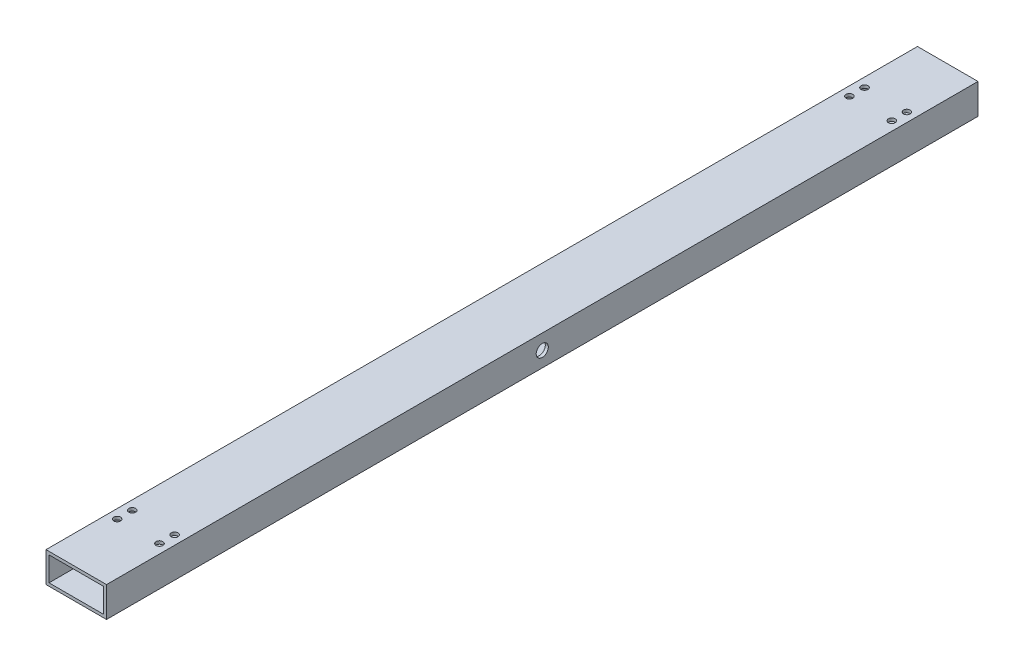
SolidWorks part; units mm, degrees
ref_plane "Front Plane" through (0, 0, 0) normal (0, 0, 1) x (1, 0, 0)
ref_plane "Top Plane" through (0, 0, 0) normal (0, 1, 0) x (1, 0, 0)
ref_plane "Right Plane" through (0, 0, 0) normal (1, 0, 0) x (0, 0, -1)
sketch "Sketch1" plane through (0, 0, 0) normal (0, 0, 1) x (1, 0, 0)
  line L0 (31.75, 0) -> (28.575, 0) construction
  line L1 (-31.75, 0) -> (31.75, 0) construction
  line L2 (0, 15.875) -> (0, -15.875)
  point P7 (0, 0)
  dimension "Width" = 63.5
  dimension "Wall Thickness" = 3.175
  dimension "Height" = 31.75
sketch "Sketch2" plane through (0, 0, 0) normal (1, 0, 0) x (0, 0, -1)
  line L0 (457.2, 0) -> (-457.2, 0)
  point P4 (0, 0)
  dimension "Length" = 914.4
sketch "Sketch3" plane through (0, 0, 0) normal (0, 0, 1) x (1, 0, 0)
  line L0 (0, 12.7) -> (0, 15.875) construction
  line L1 (-31.75, 15.875) -> (31.75, 15.875)
  line L2 (-31.75, 15.875) -> (-31.75, -15.875)
  line L3 (-31.75, -15.875) -> (31.75, -15.875)
  line L4 (31.75, 15.875) -> (31.75, -15.875)
  line L5 (-31.75, 15.875) -> (31.75, -15.875) construction
  line L6 (-31.75, -15.875) -> (31.75, 15.875) construction
  line L7 (-28.575, 12.7) -> (28.575, 12.7)
  line L8 (-28.575, 12.7) -> (-28.575, -12.7)
  line L9 (-28.575, -12.7) -> (28.575, -12.7)
  line L10 (28.575, 12.7) -> (28.575, -12.7)
  line L11 (-28.575, 12.7) -> (28.575, -12.7) construction
  line L12 (-28.575, -12.7) -> (28.575, 12.7) construction
  line L13 (31.75, 0) -> (28.575, 0) construction
  line L14 (31.75, 0) -> (28.575, 0) construction
  point P0 (0, 0)
  point P8 (0, 0)
extrude "Boss-Extrude1" add sketch "Sketch3" along normal up to vertex (457.2 mm away) and the other way up to vertex (457.2 mm away) up to point (0, 0, 457.2) other way up to point (0, 0, -457.2)
sketch "Sketch4" plane through (0, 0, 0) normal (0, 0, 1) x (1, 0, 0)
  line L0 (31.75, -15.875) -> (28.575, -15.875) construction
  line L1 (31.75, -15.875) -> (31.75, 15.875) construction
  line L2 (28.575, -12.7) -> (28.575, 12.7) construction
  line L3 (-31.75, -15.875) -> (31.75, -15.875) construction
sketch "Sketch5" plane through (0, -15.875, 0) normal (0, -1, 0) x (1, 0, 0)
  line L1 (-28.575, 384.175) -> (28.575, 384.175)
  line L2 (-28.575, 384.175) -> (-28.575, 400.05)
  line L3 (-28.575, 400.05) -> (28.575, 400.05)
  line L4 (28.575, 384.175) -> (28.575, 400.05)
  line L5 (-28.575, 384.175) -> (28.575, 400.05) construction
  line L6 (-28.575, 400.05) -> (28.575, 384.175) construction
  line L7 (-31.75, 457.2) -> (31.75, 457.2) construction
  line L8 (-31.75, 0) -> (31.75, 0) construction
  line L9 (-31.75, 457.2) -> (-31.75, -457.2) construction
  line L10 (31.75, 457.2) -> (31.75, -457.2) construction
  circle A0 centre (-22.225, 392.1125) radius 3.5719
  circle A1 centre (22.225, 392.1125) radius 3.5719
  circle A2 centre (22.225, -392.1125) radius 3.5719
  circle A3 centre (-22.225, -392.1125) radius 3.5719
  circle A4 centre (22.225, 376.2375) radius 3.5719
  circle A5 centre (-22.225, 376.2375) radius 3.5719
  circle A6 centre (22.225, -376.2375) radius 3.5719
  circle A7 centre (-22.225, -376.2375) radius 3.5719
  point P0 (0, 392.1125)
  dimension "D3" = 7.1437
  dimension "D4" = 7.1437
  dimension "D1" = 57.15
  dimension "D2" = 15.875
  dimension "D5" = 22.225
  dimension "D6" = 22.225
  dimension "D7" = 44.45
  dimension "D8" = 57.15
  dimension "D9" = 15.875
extrude "Cut-Extrude1" cut sketch "Sketch5" against normal through all contours A0 | A1 | A3 | A2 | A7 | A6 | A4 | A5
sketch "Sketch6" plane through (-31.75, 0, 0) normal (-1, 0, 0) x (0, 0, 1)
  circle A0 centre (0, 0) radius 6.35
  dimension "D1" = 12.7
extrude "Cut-Extrude2" cut sketch "Sketch6" against normal through all
sketch "Sketch7" plane through (0, 15.875, 0) normal (0, 1, 0) x (1, 0, 0)
  line L0 (0, 493.1857) -> (0, -485.0339)
  line L1 (-303.9468, 4.0759) -> (319.0859, 4.0759)
